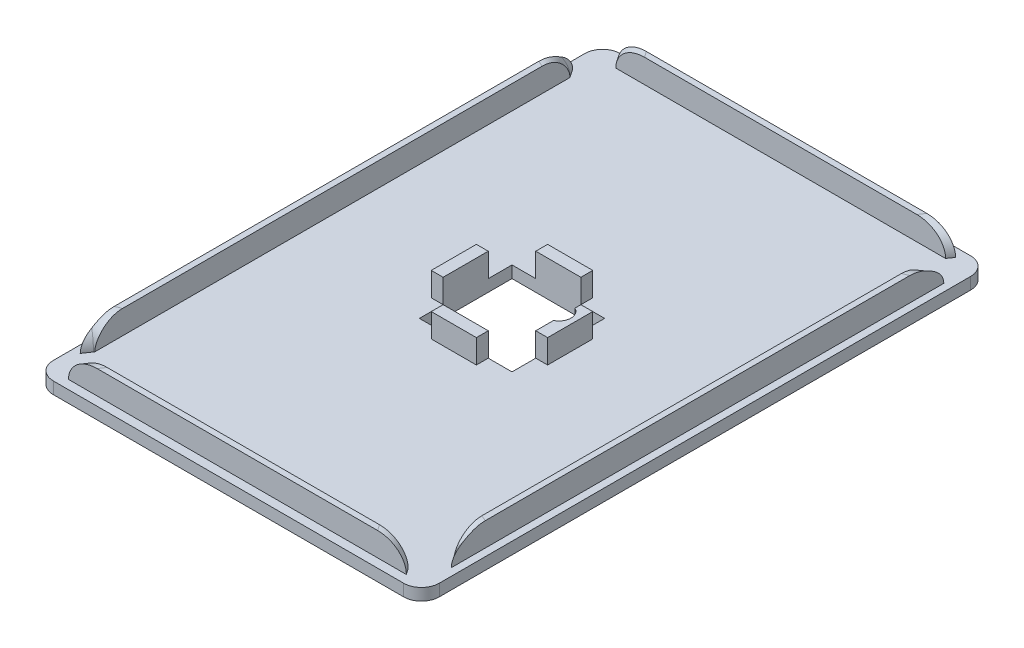
SolidWorks part; units mm, degrees
ref_plane "Front Plane" through (0, 0, 0) normal (0, 0, 1) x (1, 0, 0)
ref_plane "Top Plane" through (0, 0, 0) normal (0, 1, 0) x (1, 0, 0)
ref_plane "Right Plane" through (0, 0, 0) normal (1, 0, 0) x (0, 0, -1)
ref_axis "Axis1" through (0, 14.7, 0) along (0, -1, 0)
sketch "Sketch1" plane through (0, 0, 0) normal (0, 1, 0) x (1, 0, 0)
  line L1 (-31.25, -46.25) -> (31.25, -46.25)
  line L2 (-31.25, -46.25) -> (-31.25, 46.25)
  line L3 (-31.25, 46.25) -> (31.25, 46.25)
  line L4 (31.25, -46.25) -> (31.25, 46.25)
  line L5 (-31.25, -46.25) -> (31.25, 46.25) construction
  line L6 (-31.25, 46.25) -> (31.25, -46.25) construction
  line L7 (-32.5, 47.75) -> (32.5, 47.75)
  line L8 (-32.5, 47.75) -> (-32.5, -47.75)
  line L9 (-32.5, -47.75) -> (32.5, -47.75)
  line L10 (32.5, 47.75) -> (32.5, -47.75)
  line L11 (-32.5, 47.75) -> (32.5, -47.75) construction
  line L12 (-32.5, -47.75) -> (32.5, 47.75) construction
  point P0 (0, 0)
  point P6 (0, 0)
  dimension "D1" = 62.5
  dimension "D2" = 92.5
  dimension "D3" = 65
  dimension "D4" = 95.5
extrude "Boss-Extrude1" add sketch "Sketch1" along normal blind 2 contours L7 L10 L9 L8
extrude "Boss-Extrude2" add sketch "Sketch1<3>" along normal blind 6 contours L1 L4 L3 L2 region at (0, 0, 0)
sketch "Sketch1<3>" plane through (0, 0, 0) normal (0, 1, 0) x (1, 0, 0) same geometry as "Sketch1"
sketch "Sketch2" plane through (0, 0, 0) normal (0, 1, 0) x (1, 0, 0)
  line L0 (7.8, 7.8) -> (7.8, 2.8) construction
  line L1 (-7.8, 7.8) -> (7.8, 7.8)
  line L2 (-7.8, 7.8) -> (-7.8, -7.8)
  line L3 (-7.8, -7.8) -> (7.8, -7.8)
  line L4 (7.8, 7.8) -> (7.8, -7.8)
  line L5 (-7.8, 7.8) -> (7.8, -7.8) construction
  line L6 (-7.8, -7.8) -> (7.8, 7.8) construction
  line L7 (7.8, -7.8) -> (7.8, -0.8) construction
  line L8 (7.8, 2.8) -> (7.8, -0.8)
  line L12 (-9.8, -9.8) -> (9.8, -9.8)
  line L13 (9.8, 9.8) -> (9.8, -9.8)
  line L14 (-9.8, 9.8) -> (9.8, 9.8)
  line L15 (-9.8, 9.8) -> (-9.8, -9.8)
  arc A0 (7.8, -0.8) -> (7.8, 2.8) centre (6.9282, 1) ccw
  circle A1 centre (0, 0) radius 8.15
  point P0 (0, 0)
  dimension "D3" = 4
  dimension "D7" = 16.3
  dimension "D1" = 15.6
  dimension "D2" = 15.6
  dimension "D4" = 5
  dimension "D5" = 7
  dimension "D6" = 2
extrude "Boss-Extrude3" add sketch "Sketch2<4>" along normal blind 6 contours L13 L14 L15 L12
sketch "Sketch2<4>" plane through (0, 0, 0) normal (0, 1, 0) x (1, 0, 0) same geometry as "Sketch2"
extrude "Cut-Extrude2" cut sketch "Sketch2" along normal blind 39 contours L4 A0 | L3 L4 L1 L2 | A0 L8 region at (7.9471, 0, -0.5129)
sketch "Sketch3" plane through (0, 0, 0) normal (0, 1, 0) x (1, 0, 0)
  line L3 (-34.5667, 46.3433) -> (-30.3467, 40.1432)
  line L4 (30.4333, 49.1567) -> (26.2133, 42.9565)
  line L5 (-30.4333, 49.1567) -> (-26.2133, 42.9565)
  line L6 (34.5667, 46.3433) -> (30.3467, 40.1432)
  line L7 (-34.5667, -46.3433) -> (-30.4333, -49.1567)
  line L8 (30.4333, -49.1567) -> (34.5667, -46.3433)
  line L9 (30.4333, 49.1567) -> (34.5667, 46.3433)
  line L10 (-30.4333, 49.1567) -> (-34.5667, 46.3433)
  line L18 (30.3467, -40.1432) -> (34.5667, -46.3433)
  line L20 (0, 23.1046) -> (0, -27.3759) construction
  line L21 (0, -7.7) -> (0, 7.7) construction
  line L22 (26.2133, -42.9565) -> (30.4333, -49.1567)
  line L23 (-26.2133, -42.9565) -> (-30.4333, -49.1567)
  line L24 (-30.3467, -40.1432) -> (-34.5667, -46.3433)
  circle A0 centre (-28.28, 41.5499) radius 2.5
  circle A1 centre (28.28, 41.5499) radius 2.5
  circle A2 centre (-28.28, -41.5499) radius 2.5
  circle A3 centre (28.28, -41.5499) radius 2.5
  point P27 (0, 0)
  dimension "D3" = 5
  dimension "D6" = 5
  dimension "D7" = 5
extrude "Cut-Extrude3" cut sketch "Sketch3" along normal blind 8 from offset 2 contours A2 | A2 L24 L7 L23 | A0 L5 L10 L3 | A0 | A1 L6 L9 L4 | A3 | A3 L22 L8 L18 | A1 region at (-30.9266, 0, -45.4383) region at (-28.28, 0, -41.5499) region at (30.9266, 0, -45.4383) region at (-30.9266, 0, 45.4383) region at (-28.28, 0, 41.5499) region at (30.9266, 0, 45.4383) region at (28.28, 0, 41.5499)
fillet "Fillet1" radius 4 12 edges at (-30.7984, 6, 40.8068) (-27.3341, 6, 44.6033) (27.3341, 6, 44.6033) (30.7984, 6, 40.8068) (30.7984, 6, -40.8068) (27.3341, 6, -44.6033) (-27.3341, 6, -44.6033) (-30.7984, 6, -40.8068) (-26.8733, 6, 39.4832) (26.8733, 6, 39.4832) (26.8733, 6, -39.4832) (-26.8733, 6, -39.4832)
sketch "Sketch5" plane through (0, 6, 0) normal (0, 1, 0) x (1, 0, 0)
  line L16 (-21.7563, -45.25) -> (21.7563, -45.25)
  line L17 (30.25, -34.3132) -> (30.25, 34.3132)
  line L18 (21.7563, 45.25) -> (-21.7563, 45.25)
  line L19 (-30.25, 34.3132) -> (-30.25, -34.3132)
  line L20 (-21.7563, -45.25) -> (21.7563, -45.25)
  line L21 (30.25, -34.3132) -> (30.25, 34.3132)
  line L22 (21.7563, 45.25) -> (-21.7563, 45.25)
  line L23 (-30.25, 34.3132) -> (-30.25, -34.3132)
  line L26 (9.8, -9.8) -> (-9.8, -9.8)
  line L30 (-9.8, 9.8) -> (-9.8, -9.8)
  line L31 (9.8, 9.8) -> (-9.8, 9.8)
  line L32 (9.8, 9.8) -> (9.8, -9.8)
  line L33 (-21.7563, 45.25) -> (-30.25, 45.25)
  line L34 (-30.25, 45.25) -> (-30.25, 34.3132)
  line L35 (21.7563, 45.25) -> (30.25, 45.25)
  line L36 (30.25, 45.25) -> (30.25, 34.3132)
  line L37 (21.7563, -45.25) -> (30.25, -45.25)
  line L38 (30.25, -45.25) -> (30.25, -34.3132)
  line L39 (-30.25, -45.25) -> (-30.25, -34.3132)
  line L40 (-21.7563, -45.25) -> (-30.25, -45.25)
  arc A8 (-21.7563, -45.25) -> (-30.25, -34.3132) centre (-28.28, -41.5499) ccw
  arc A9 (30.25, -34.3132) -> (21.7563, -45.25) centre (28.28, -41.5499) ccw
  arc A10 (21.7563, 45.25) -> (30.25, 34.3132) centre (28.28, 41.5499) ccw
  arc A11 (-30.25, 34.3132) -> (-21.7563, 45.25) centre (-28.28, 41.5499) ccw
  arc A12 (-21.7563, -45.25) -> (-30.25, -34.3132) centre (-28.28, -41.5499) ccw construction
  arc A13 (30.25, -34.3132) -> (21.7563, -45.25) centre (28.28, -41.5499) ccw construction
  arc A14 (21.7563, 45.25) -> (30.25, 34.3132) centre (28.28, 41.5499) ccw construction
  arc A15 (-30.25, 34.3132) -> (-21.7563, 45.25) centre (-28.28, 41.5499) ccw construction
  dimension "D1" = 1
sketch "Sketch7" plane through (0, 0, 0) normal (0, 1, 0) x (1, 0, 0)
  line L0 (7.8, 7.8) -> (7.8, -7.8) construction
  line L1 (7.8, 2.8) -> (7.8, -0.8)
  arc A0 (7.8, -0.8) -> (7.8, 2.8) centre (6.9282, 1) ccw construction
  arc A1 (7.8, -0.8) -> (7.8, 2.8) centre (6.9282, 1) ccw
extrude "Boss-Extrude4" add sketch "Sketch7" along normal blind 1
extrude "Cut-Extrude7" cut sketch "Sketch5" against normal blind 4
fillet "Fillet2" radius 3 4 edges at (-32.5, 1, -47.75) (32.5, 1, -47.75) (-32.5, 1, 47.75) (32.5, 1, 47.75)
sketch "Sketch9" plane through (0, 2, 0) normal (0, 1, 0) x (1, 0, 0)
  line L1 (-9.8, 9.8) -> (-3.8, 9.8)
  line L2 (-9.8, 9.8) -> (-9.8, 3.8)
  line L3 (-9.8, 3.8) -> (-3.8, 3.8)
  line L4 (-3.8, 9.8) -> (-3.8, 3.8)
  line L5 (-9.8, -9.8) -> (-3.8, -9.8)
  line L6 (-9.8, -9.8) -> (-9.8, -3.8)
  line L7 (-9.8, -3.8) -> (-3.8, -3.8)
  line L8 (-3.8, -9.8) -> (-3.8, -3.8)
  line L9 (9.8, -9.8) -> (3.8, -9.8)
  line L10 (9.8, -9.8) -> (9.8, -3.8)
  line L11 (9.8, -3.8) -> (3.8, -3.8)
  line L12 (3.8, -9.8) -> (3.8, -3.8)
  line L13 (9.8, 9.8) -> (3.8, 9.8)
  line L14 (9.8, 9.8) -> (9.8, 3.8)
  line L15 (9.8, 3.8) -> (3.8, 3.8)
  line L16 (3.8, 9.8) -> (3.8, 3.8)
  dimension "D1" = 6
  dimension "D2" = 6
  dimension "D3" = 6
  dimension "D4" = 6
  dimension "D5" = 6
  dimension "D6" = 6
  dimension "D7" = 6
  dimension "D8" = 6
extrude "Cut-Extrude8" cut sketch "Sketch9" along normal blind 10 contours L3 L4 L1 L2 | L5 L8 L7 L6 | L9 L12 L11 L10 | L15 L16 L13 L14
